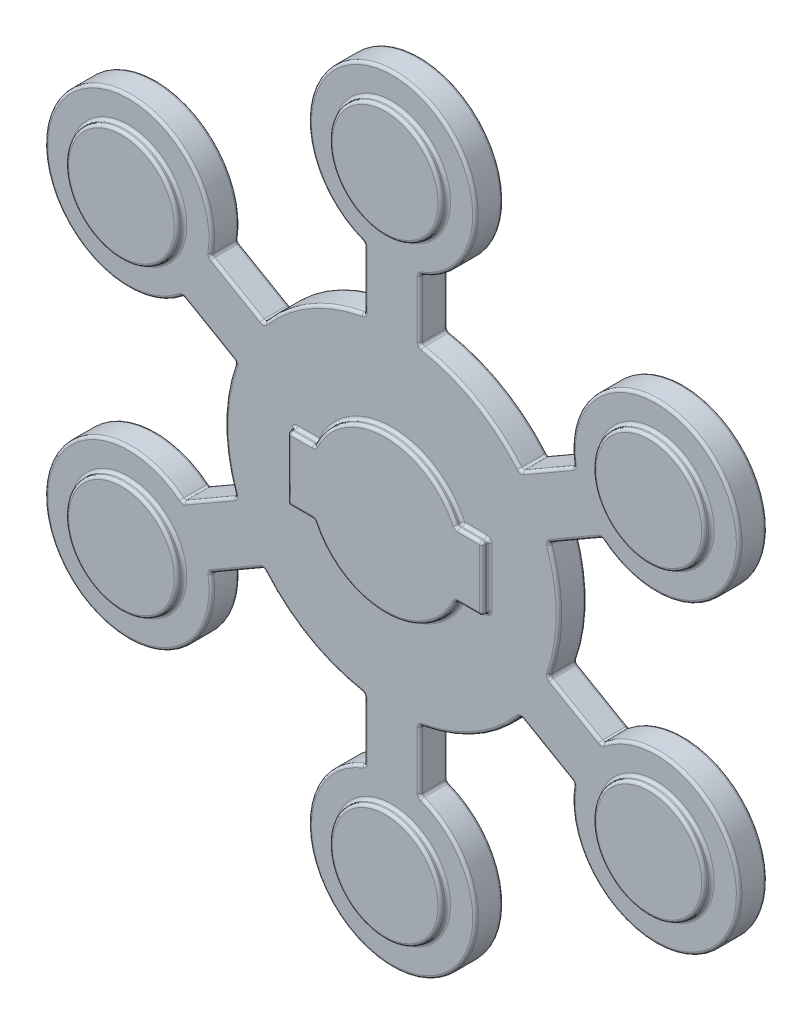
SolidWorks part; units mm, degrees
ref_plane "Front Plane" through (0, 0, 0) normal (0, 0, 1) x (1, 0, 0)
ref_plane "Top Plane" through (0, 0, 0) normal (0, 1, 0) x (1, 0, 0)
ref_plane "Right Plane" through (0, 0, 0) normal (1, 0, 0) x (0, 0, -1)
sketch "Sketch1" plane through (0, 0, 0) normal (0, 0, 1) x (1, 0, 0)
  line L0 (0, 0) -> (50000, 0) construction
  line L1 (0, 2.4215) -> (0, 50002.4215) construction
  line L2 (10, 59.1608) -> (10, 81.2157)
  line L3 (-10, 59.1608) -> (-10, 81.2157)
  line L4 (25.5294, 11.5) -> (35, 11.5)
  line L5 (35, 11.5) -> (35, -11.5)
  line L6 (35, -11.5) -> (25.5294, -11.5)
  line L7 (-35, -11.5) -> (-25.5294, -11.5)
  line L8 (-35, 11.5) -> (-35, -11.5)
  line L9 (-25.5294, 11.5) -> (-35, 11.5)
  line L10 (56.2348, 20.9201) -> (75.3349, 31.9476)
  line L11 (46.2348, 38.2407) -> (65.3349, 49.2681)
  line L12 (46.2348, -38.2407) -> (65.3349, -49.2681)
  line L13 (56.2348, -20.9201) -> (75.3349, -31.9476)
  line L14 (-10, -59.1608) -> (-10, -81.2157)
  line L15 (10, -59.1608) -> (10, -81.2157)
  line L16 (-56.2348, -20.9201) -> (-75.3349, -31.9476)
  line L17 (-46.2348, -38.2407) -> (-65.3349, -49.2681)
  line L18 (-46.2348, 38.2407) -> (-65.3349, 49.2681)
  line L19 (-56.2348, 20.9201) -> (-75.3349, 31.9476)
  arc A0 (-25.5294, -11.5) -> (25.5294, -11.5) centre (0, 0) ccw
  arc A1 (-56.2348, 20.9201) -> (-56.2348, -20.9201) centre (0, 0) ccw
  circle A2 centre (0, 0) radius 109.5 construction
  circle A3 centre (0, 109.5) radius 20
  arc A4 (10, 81.2157) -> (-10, 81.2157) centre (0, 109.5) ccw
  arc A5 (25.5294, 11.5) -> (-25.5294, 11.5) centre (0, 0) ccw
  circle A6 centre (94.8298, 54.75) radius 20
  arc A7 (75.3349, 31.9476) -> (65.3349, 49.2681) centre (94.8298, 54.75) ccw
  circle A8 centre (94.8298, -54.75) radius 20
  arc A9 (65.3349, -49.2681) -> (75.3349, -31.9476) centre (94.8298, -54.75) ccw
  circle A10 centre (0, -109.5) radius 20
  arc A11 (-10, -81.2157) -> (10, -81.2157) centre (0, -109.5) ccw
  circle A12 centre (-94.8298, -54.75) radius 20
  arc A13 (-75.3349, -31.9476) -> (-65.3349, -49.2681) centre (-94.8298, -54.75) ccw
  circle A14 centre (-94.8298, 54.75) radius 20
  arc A15 (-65.3349, 49.2681) -> (-75.3349, 31.9476) centre (-94.8298, 54.75) ccw
  arc A16 (-46.2348, -38.2407) -> (-10, -59.1608) centre (0, 0) ccw
  arc A17 (10, -59.1608) -> (46.2348, -38.2407) centre (0, 0) ccw
  arc A18 (56.2348, -20.9201) -> (56.2348, 20.9201) centre (0, 0) ccw
  arc A19 (46.2348, 38.2407) -> (10, 59.1608) centre (0, 0) ccw
  arc A20 (-46.2348, 38.2407) -> (-10.7044, 59.0374) centre (0, 0) cw
  circle A21 centre (0, 0) radius 60
  point P20 (30.2647, -11.5)
  point P55 (0, 0)
  dimension "D1" = 56
  dimension "D2" = 120
  dimension "D3" = 219
  dimension "D4" = 40
  dimension "D5" = 60
  dimension "D10" = 120
  dimension "D6" = 20
  dimension "D7" = 23
  dimension "D8" = 35
  dimension "D9" = 6
extrude "Boss-Extrude1" add sketch "Sketch1" along normal mid plane 15 contours A14 | A3 | A6 | A8 | A10 | A12 | L4 A5 L9 L8 L7 A0 L6 L5 region at (0, 0, 0) region at (0, 109.5, 0) region at (94.8298, 54.75, 0) region at (94.8298, -54.75, 0) region at (0, -109.5, 0) region at (-94.8298, -54.75, 0) region at (-94.8298, 54.75, 0)
extrude "Boss-Extrude2" add sketch "Sketch1<4>" along normal mid plane 10 contours A18 A21 A19 A20 A1 A16 A17 A5 L4 L5 L6 A0 L7 L8 L9 | A21 L18 A15 L19 A14 | A21 L2 A4 L3 A3 | A21 L10 A7 L11 A6 | A21 L12 A9 L13 A8 | A21 L14 A11 L15 A10 | A21 L16 A13 L17 A12 region at (0, 61.0027, 0) region at (29.1515, 50.4918, 0) region at (56.2911, 42.8775, 0) region at (-52.8384, 30.5062, 0) region at (65.2786, -27.3107, 0) region at (-52.8384, -30.5062, 0) region at (8.9973, -70.1883, 0)
sketch "Sketch1<4>" plane through (0, 0, 0) normal (0, 0, 1) x (1, 0, 0) same geometry as "Sketch1"
fillet "Fillet1" radius 1 144 edges at (0, 139.5, 5) (0, 139.5, -5) (-74.8298, 54.75, -5) (-74.8298, 54.75, 7.5) (-74.8298, 54.75, -7.5) (56.2348, 20.9201, 0) (75.3349, 31.9476, 0) (65.3349, 49.2681, 0) (46.2348, 38.2407, 0) (10, 59.1608, 0) (10, 81.2157, 0) (-10, 81.2157, 0) (-10, 59.1608, 0) (-46.2348, 38.2407, 0) (-65.3349, 49.2681, 0) (-75.3349, 31.9476, 0) (-56.2348, 20.9201, 0) (-56.2348, -20.9201, 0) (-75.3349, -31.9476, 0) (-65.3349, -49.2681, 0) (-46.2348, -38.2407, 0) (-10, -59.1608, 0) (-10, -81.2157, 0) (10, -81.2157, 0) (10, -59.1608, 0) (46.2348, -38.2407, 0) (65.3349, -49.2681, 0) (75.3349, -31.9476, 0) (56.2348, -20.9201, 0) (114.8298, 54.75, 5) (20, 109.5, 5) (-74.8298, 54.75, 5) (-74.8298, -54.75, 5) (20, -109.5, 5) (114.8298, -54.75, 5) (65.7848, -26.4339, 5) (120.8105, -69.75, 5) (55.7848, -43.7544, 5) (30, -51.9615, 5) (10, -70.1883, 5) (0, -139.5, 5) (-10, -70.1883, 5) (-30, -51.9615, 5) (-55.7848, -43.7544, 5) (-120.8105, -69.75, 5) (-65.7848, -26.4339, 5) (-60, 0, 5) (-65.7848, 26.4339, 5) (-120.8105, 69.75, 5) (-55.7848, 43.7544, 5) (-30, 51.9615, 5) (-10, 70.1883, 5) (10, 70.1883, 5) (30, 51.9615, 5) (55.7848, 43.7544, 5) (120.8105, 69.75, 5) (65.7848, 26.4339, 5) (60, 0, 5) (-30.2647, 11.5, 5) (-35, 0, 5) (-30.2647, -11.5, 5) (0, -28, 5) (30.2647, -11.5, 5) (35, 0, 5) (30.2647, 11.5, 5) (0, 28, 5) (65.7848, -26.4339, -5) (120.8105, -69.75, -5) (55.7848, -43.7544, -5) (30, -51.9615, -5) (10, -70.1883, -5) (0, -139.5, -5) (-10, -70.1883, -5) (-30, -51.9615, -5) (-55.7848, -43.7544, -5) (-120.8105, -69.75, -5) (-65.7848, -26.4339, -5) (-60, 0, -5) (-65.7848, 26.4339, -5) (-120.8105, 69.75, -5) (-55.7848, 43.7544, -5) (-30, 51.9615, -5) (-10, 70.1883, -5) (10, 70.1883, -5) (30, 51.9615, -5) (55.7848, 43.7544, -5) (120.8105, 69.75, -5) (65.7848, 26.4339, -5) (60, 0, -5) (-30.2647, 11.5, -5) (-35, 0, -5) (-30.2647, -11.5, -5) (0, -28, -5) (30.2647, -11.5, -5) (35, 0, -5) (30.2647, 11.5, -5) (0, 28, -5) (20, 109.5, -5) (20, 109.5, 7.5) (20, 109.5, -7.5) (114.8298, 54.75, -5) (114.8298, 54.75, 7.5) (114.8298, 54.75, -7.5) (114.8298, -54.75, -5) (114.8298, -54.75, 7.5) (114.8298, -54.75, -7.5) (20, -109.5, -5) (20, -109.5, 7.5) (20, -109.5, -7.5) (-74.8298, -54.75, -5) (-74.8298, -54.75, 7.5) (-74.8298, -54.75, -7.5) (25.5294, 11.5, 6.25) (25.5294, 11.5, -6.25) (-25.5294, 11.5, 6.25) (-25.5294, 11.5, -6.25) (-35, 11.5, 6.25) (-35, 11.5, -6.25) (-35, -11.5, 6.25) (-35, -11.5, -6.25) (-25.5294, -11.5, 6.25) (-25.5294, -11.5, -6.25) (25.5294, -11.5, 6.25) (25.5294, -11.5, -6.25) (35, -11.5, 6.25) (35, -11.5, -6.25) (35, 11.5, 6.25) (35, 11.5, -6.25) (35, 0, 7.5) (30.2647, -11.5, 7.5) (0, -28, 7.5) (-30.2647, -11.5, 7.5) (-35, 0, 7.5) (-30.2647, 11.5, 7.5) (0, 28, 7.5) (30.2647, 11.5, 7.5) (35, 0, -7.5) (30.2647, -11.5, -7.5) (0, -28, -7.5) (-30.2647, -11.5, -7.5) (-35, 0, -7.5) (-30.2647, 11.5, -7.5) (0, 28, -7.5) (30.2647, 11.5, -7.5)
